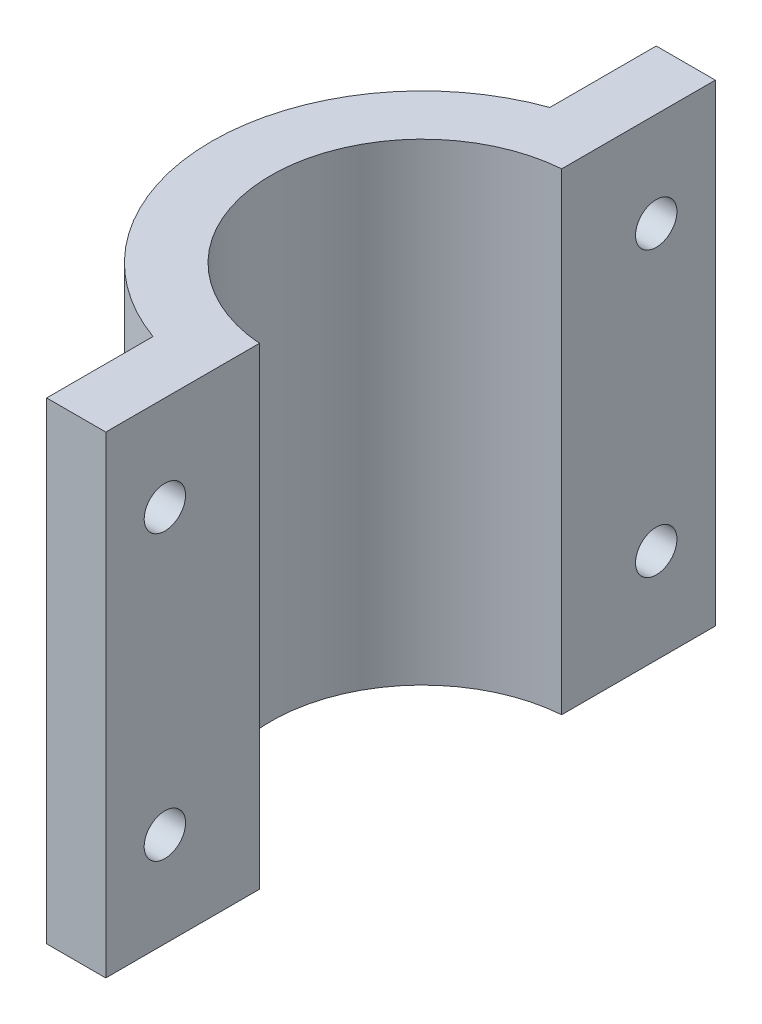
SolidWorks part; units mm, degrees
ref_plane "Front Plane" through (0, 0, 0) normal (0, 0, 1) x (1, 0, 0)
ref_plane "Top Plane" through (0, 0, 0) normal (0, 1, 0) x (1, 0, 0)
ref_plane "Right Plane" through (0, 0, 0) normal (1, 0, 0) x (0, 0, -1)
sketch "Sketch6" plane through (0, 0, 0) normal (0, -1, 0) x (1, 0, 0)
  line L5 (-1, 25.7848) -> (-1, 12.786)
  line L6 (-1, 25.7848) -> (-6, 25.7848)
  line L7 (-6, 25.7848) -> (-6, 16.7848)
  line L8 (-6, -16.7848) -> (-6, -25.7848)
  line L9 (-6, -25.7848) -> (-1, -25.7848)
  line L10 (-1, -25.7848) -> (-1, -12.786)
  line L11 (-12.825, 0) -> (-17.825, 0) construction
  arc A0 (-1, 12.786) -> (-1, -12.786) centre (0, 0) ccw
  arc A1 (-6, 16.7848) -> (-6, -16.7848) centre (0, 0) ccw
  dimension "D1" = 25.65
  dimension "D2" = 5
  dimension "D3" = 1
  dimension "D4" = 9
extrude "Boss-Extrude4" add sketch "Sketch6" along normal blind 40
sketch "Sketch7" plane through (-1, 0, 0) normal (1, 0, 0) x (0, 0, -1)
  line L0 (-20.7848, -40) -> (-20.7848, 0) construction
  line L1 (-12.786, -40) -> (-25.7848, -40) construction
  line L2 (-25.7848, -20) -> (25.7848, -20) construction
  line L3 (0, 0) -> (0, -40) construction
  line L4 (25.7848, -40) -> (25.7848, 0) construction
  line L6 (-25.7848, -8) -> (25.7848, -8) construction
  line L13 (-25.7848, -40) -> (-25.7848, 0) construction
  line L15 (-12.786, -40) -> (12.786, -40) construction
  circle A1 centre (-20.7848, -8) radius 1.75
  circle A2 centre (20.7848, -8) radius 1.75
  circle A3 centre (20.7848, -32) radius 1.75
  circle A4 centre (-20.7848, -32) radius 1.75
  dimension "D1" = 3.5
  dimension "D2" = 5
  dimension "D3" = 12
extrude "Cut-Extrude1" cut sketch "Sketch7" against normal through all
